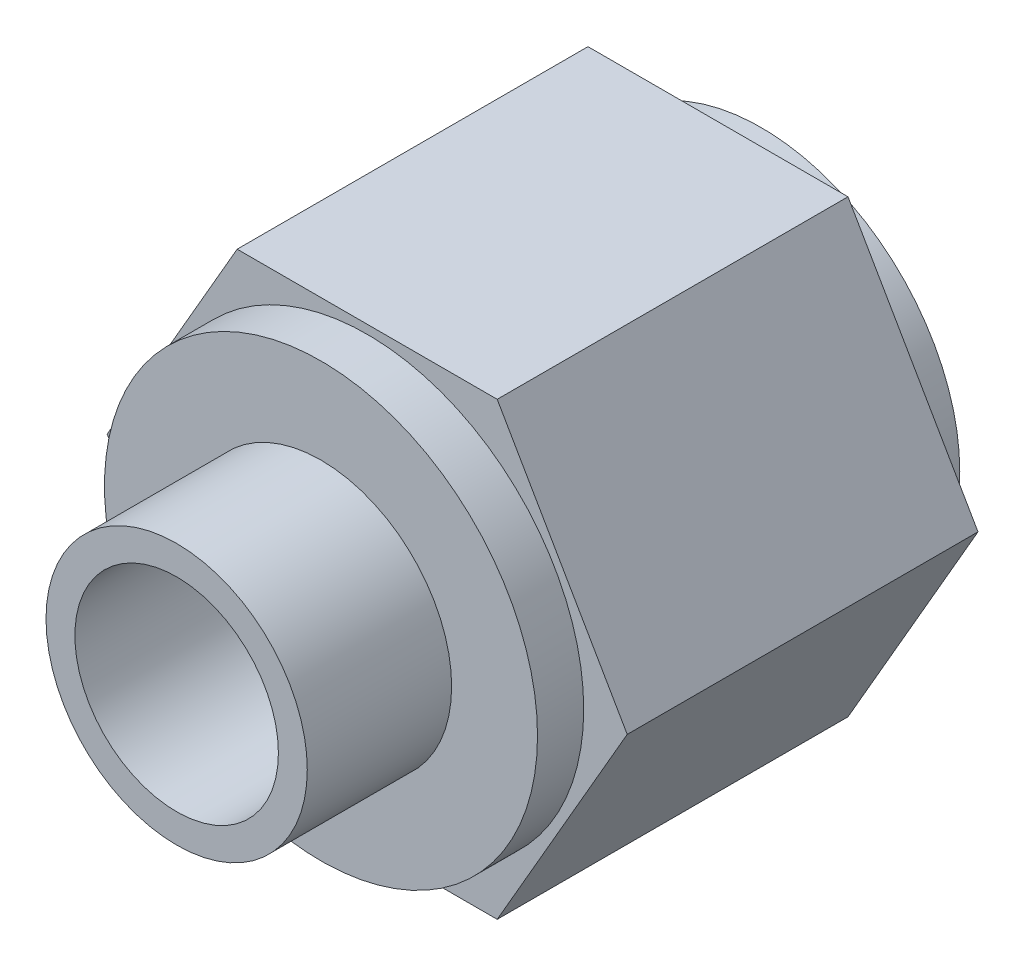
SolidWorks part; units mm, degrees
ref_plane "Front Plane" through (0, 0, 0) normal (0, 0, 1) x (1, 0, 0)
ref_plane "Top Plane" through (0, 0, 0) normal (0, 1, 0) x (1, 0, 0)
ref_plane "Right Plane" through (0, 0, 0) normal (1, 0, 0) x (0, 0, -1)
ref_plane "Plane1" through (0, 0, -3.3528) normal (0, 0, 1) x (1, 0, 0)
sketch "Sketch1" plane through (0, 0, -3.3528) normal (0, 0, 1) x (1, 0, 0)
  line L0 (-4.5754, 0) -> (-2.2877, -3.9624)
  line L1 (-2.2877, -3.9624) -> (2.2877, -3.9624)
  line L2 (2.2877, -3.9624) -> (4.5754, 0)
  line L3 (4.5754, 0) -> (2.2877, 3.9624)
  line L4 (2.2877, 3.9624) -> (-2.2877, 3.9624)
  line L5 (-2.2877, 3.9624) -> (-4.5754, 0)
extrude "Extrude1" add sketch "Sketch1" against normal blind 6.1722
sketch "Sketch2" plane through (0, 0, -3.3528) normal (0, 0, 1) x (1, 0, 0)
  circle A0 centre (0, 0) radius 3.81
extrude "Extrude2" add sketch "Sketch2" along normal blind 0.8128
sketch "Sketch3" plane through (0, 0, -2.54) normal (0, 0, 1) x (1, 0, 0)
  circle A0 centre (0, 0) radius 2.2987
extrude "Extrude3" add sketch "Sketch3" along normal blind 2.54
sketch "Sketch4" plane through (0, 0, -9.525) normal (0, 0, -1) x (-1, 0, 0)
  circle A0 centre (0, 0) radius 3.4925
extrude "Extrude4" add sketch "Sketch4" along normal blind 0.762
hole_wizard "Hole1" positions "Sketch6" profile "Sketch5" legacy
sketch "Sketch6" plane through (0, 0, -10.287) normal (0, 0, -1) x (-1, 0, 0)
  point P0 (0, 0)
sketch "Sketch5" plane through (0, 0, -10.287) normal (1, 0, 0) x (0, 1, 0)
  line L0 (0, 0) -> (0, 2.7686)
  line L1 (0, 2.7686) -> (3.175, 2.7686)
  line L2 (3.175, 2.7686) -> (3.175, 0)
  line L3 (3.175, 0) -> (0, 0)
  line L4 (0, 110) -> (0, -10) construction
  dimension "Diameter" = 6.35
  dimension "Depth" = 2.7686
sketch "Sketch7" plane through (0, 0, -7.5184) normal (0, 0, -1) x (-1, 0, 0)
  circle A0 centre (0, 0) radius 0.381
extrude "Extrude5" add sketch "Sketch7" along normal blind 2.2352
other "CPoint1" parameters "Diameter"=3.5814
ref_axis "Axis1" through (0, 0, 10) along (0, 0, -1)
sketch "Sketch8" plane through (0, 0, 0) normal (0, 0, 1) x (1, 0, 0)
  circle A0 centre (0, 0) radius 1.7907
extrude "Cut-Extrude1" cut sketch "Sketch8" along direction (0, 0, 1) on the side against the normal up to surface (2.54 mm away) up to face at (3.81, 0, -2.54)
